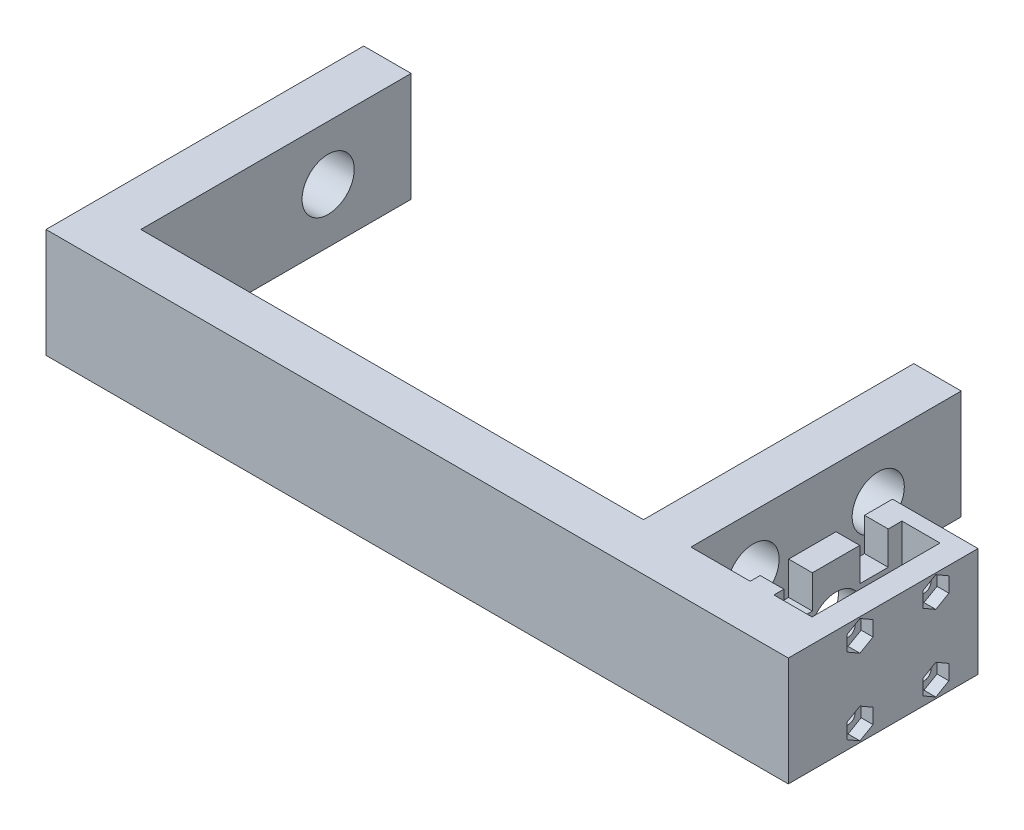
SolidWorks part; units mm, degrees
ref_plane "Front Plane" through (0, 0, 0) normal (0, 0, 1) x (1, 0, 0)
ref_plane "Top Plane" through (0, 0, 0) normal (0, 1, 0) x (1, 0, 0)
ref_plane "Right Plane" through (0, 0, 0) normal (1, 0, 0) x (0, 0, -1)
sketch "Sketch1" plane through (0, 0, 0) normal (0, 1, 0) x (1, 0, 0)
  line L0 (-50, -27.5) -> (-50, 27.5) construction
  line L1 (-40, -17.5) -> (40, -17.5) construction
  line L2 (-40, -17.5) -> (-40, 17.5) construction
  line L3 (-40, 17.5) -> (40, 17.5) construction
  line L4 (40, -17.5) -> (40, 17.5) construction
  line L5 (-40, -17.5) -> (40, 17.5) construction
  line L6 (-40, 17.5) -> (40, -17.5) construction
  line L7 (-50, 27.5) -> (50, 27.5) construction
  line L8 (50, -27.5) -> (50, 27.5) construction
  line L9 (-50, -27.5) -> (50, -27.5) construction
  line L10 (50, 0) -> (53, 0) construction
  line L11 (-50, 0) -> (-53, 0) construction
  line L12 (53, 0) -> (53, -27.5)
  line L13 (53, -27.5) -> (53, -39.5)
  line L14 (-53, 0) -> (-53, -27.5)
  line L15 (-53, -27.5) -> (-53, -39.5)
  line L16 (-53, -39.5) -> (53, -39.5)
  line L17 (53, 0) -> (53, 17.5)
  line L18 (-53, 0) -> (-53, 17.5)
  line L19 (-63, 0) -> (-63, 17.5)
  line L20 (-63, 0) -> (-63, -27.5)
  line L21 (-63, -27.5) -> (-63, -49.5)
  line L22 (-63, -49.5) -> (63, -49.5)
  line L23 (63, -27.5) -> (63, -49.5) construction
  line L24 (63, 0) -> (63, -27.5)
  line L25 (63, 0) -> (63, 17.5)
  line L26 (-53, 17.5) -> (-63, 17.5)
  line L27 (53, 17.5) -> (63, 17.5)
  line L28 (88.54, -39.5) -> (88.54, -9.5)
  line L29 (63, -49.5) -> (88.54, -49.5)
  line L31 (63, -39.5) -> (88.54, -39.5)
  line L32 (88.54, -49.5) -> (88.54, -39.5) construction
  line L33 (88.54, -49.5) -> (93.54, -49.5)
  line L34 (88.54, -49.5) -> (88.54, -9.5) construction
  line L35 (88.54, -9.5) -> (93.54, -9.5)
  line L36 (93.54, -49.5) -> (93.54, -9.5)
  line L37 (63, -39.5) -> (63, 17.5)
  line L39 (75.5, -39.5) -> (80.5, -39.5)
  line L40 (75.5, -39.5) -> (75.5, -9.5)
  line L41 (75.5, -9.5) -> (80.5, -9.5)
  line L42 (80.5, -39.5) -> (80.5, -9.5)
  line L43 (80.5, -9.5) -> (88.54, -9.5)
  line L44 (80.5, -9.5) -> (80.5, -12.5)
  line L45 (80.5, -12.5) -> (88.54, -12.5)
  line L46 (88.54, -9.5) -> (88.54, -12.5)
  point P0 (0, 0)
  point P10 (50, 0)
  point P11 (0, -27.5)
  point P12 (0, 27.5)
  point P13 (-50, 0)
  dimension "D1" = 80
  dimension "D2" = 35
  dimension "D4" = 3
  dimension "D5" = 12
  dimension "D7" = 8.04
  dimension "D8" = 5
  dimension "D9" = 12.5
  dimension "D10" = 5
  dimension "D11" = 30
  dimension "D12" = 3
  dimension "D3" = 10
  dimension "D6" = 10
extrude "Boss-Extrude1" add sketch "Sketch1" along normal mid plane 23 contours L31 L37 L24 L25 L27 L17 L12 L13 L16 L15 L14 L18 L26 L19 L20 L21 L22 L29 L33 L36 L35 L28 | L31 L42 L41 L40 | L42 L45 L28 L43 region at (54.7028, 0, -8.75) region at (78, 0, 24.5) region at (84.52, 0, 11)
sketch "Sketch2" plane through (63, 0, 0) normal (1, 0, 0) x (0, 0, -1)
  line L0 (-23.594, 0) -> (-26.9808, 0) construction
  line L1 (-23.594, 0) -> (-26.394, 0) construction
  line L4 (-39.5, -11.5) -> (17.5, -11.5)
  line L5 (17.5, -11.5) -> (17.5, 11.5)
  line L6 (-39.5, -11.5) -> (17.5, -11.5)
  line L7 (17.5, 11.5) -> (-39.5, 11.5)
  line L9 (17.5, -11.5) -> (17.5, 11.5)
  line L14 (17.5, 11.5) -> (-39.5, 11.5)
  line L15 (-39.5, 11.5) -> (-39.5, -11.5)
  line L16 (-39.5, 11.5) -> (-39.5, -11.5)
  circle A0 centre (0, 0) radius 5.5
  circle A1 centre (0, 0) radius 23.594 construction
  circle A2 centre (-26.394, 0) radius 3.3868 construction
  circle A3 centre (-26.9808, 0) radius 3.3867 construction
  circle A4 centre (-26.394, 0) radius 5.5
  dimension "D2" = 11
  dimension "D3" = 47.188
  dimension "D4" = 3.3868
  dimension "D5" = 2.8
  dimension "D1" = 0
extrude "Cut-Extrude1" cut sketch "Sketch2" against normal up to surface (126 mm away) contours A0 up to face at (-63, 0, 16)
sketch "Sketch3" plane through (63, 0, 0) normal (1, 0, 0) x (0, 0, -1)
  circle A0 centre (-26.394, 0) radius 5.5 construction
  circle A1 centre (-26.394, 0) radius 5.5
extrude "Cut-Extrude2" cut sketch "Sketch3" against normal up to next
sketch "Sketch8" plane through (75.5, 0, 0) normal (-1, 0, 0) x (0, 0, 1)
  circle A0 centre (26.394, 0) radius 5.5 construction
  circle A1 centre (26.394, 0) radius 5.5
extrude "Cut-Extrude5" cut sketch "Sketch8" against normal up to surface (5 mm away) up to face at (80.5, 0, 26)
sketch "Sketch10" plane through (88.54, 0, 0) normal (-1, 0, 0) x (0, 0, 1)
  line L1 (18.394, -8) -> (34.394, -8) construction
  line L2 (18.394, -8) -> (18.394, 8) construction
  line L3 (18.394, 8) -> (34.394, 8) construction
  line L4 (34.394, -8) -> (34.394, 8) construction
  line L5 (18.394, -8) -> (34.394, 8) construction
  line L6 (18.394, 8) -> (34.394, -8) construction
  circle A0 centre (26.394, 0) radius 5.5 construction
  circle A1 centre (26.394, 0) radius 5.5 construction
  circle A2 centre (18.394, 8) radius 1.8
  circle A3 centre (34.394, -8) radius 1.8
  circle A4 centre (18.394, -8) radius 1.8
  circle A5 centre (34.394, 8) radius 1.8
  dimension "D2" = 3.6
  dimension "D1" = 16
extrude "Boss-Extrude4" add sketch "Sketch10" along normal blind 1
sketch "Sketch11" plane through (87.54, 0, 0) normal (-1, 0, 0) x (0, 0, 1)
  circle A0 centre (18.394, 8) radius 1.5
  circle A1 centre (34.394, 8) radius 1.5
  circle A2 centre (34.394, -8) radius 1.5
  circle A3 centre (18.394, -8) radius 1.5
  dimension "D1" = 3
extrude "Cut-Extrude6" cut sketch "Sketch11" against normal up to surface (6 mm away) up to face at (93.54, 0, 29.5)
sketch "Sketch12" plane through (93.54, 0, 0) normal (1, 0, 0) x (0, 0, -1)
  line L1 (-31.644, 9.5877) -> (-34.394, 11.1754)
  line L2 (-34.394, 11.1754) -> (-37.144, 9.5877)
  line L3 (-37.144, 9.5877) -> (-37.144, 6.4123)
  line L4 (-49.5, -11.5) -> (-9.5, -11.5)
  line L5 (-9.5, -11.5) -> (-9.5, 11.5)
  line L6 (-9.5, 11.5) -> (-49.5, 11.5)
  line L7 (-49.5, 11.5) -> (-49.5, -11.5)
  line L8 (-49.5, -11.5) -> (-9.5, -11.5)
  line L9 (-9.5, -11.5) -> (-9.5, 11.5)
  line L10 (-9.5, 11.5) -> (-49.5, 11.5)
  line L11 (-49.5, 11.5) -> (-49.5, -11.5)
  line L12 (-37.144, 6.4123) -> (-34.394, 4.8246)
  line L13 (-34.394, 4.8246) -> (-31.644, 6.4123)
  line L14 (-31.644, 6.4123) -> (-31.644, 9.5877)
  line L15 (-18.394, 11.1754) -> (-21.144, 9.5877)
  line L16 (-21.144, 9.5877) -> (-21.144, 6.4123)
  line L17 (-21.144, 6.4123) -> (-18.394, 4.8246)
  line L18 (-18.394, 4.8246) -> (-15.644, 6.4123)
  line L19 (-15.644, 6.4123) -> (-15.644, 9.5877)
  line L20 (-15.644, 9.5877) -> (-18.394, 11.1754)
  line L21 (-31.644, -6.4123) -> (-34.394, -4.8246)
  line L22 (-34.394, -4.8246) -> (-37.144, -6.4123)
  line L23 (-37.144, -6.4123) -> (-37.144, -9.5877)
  line L24 (-37.144, -9.5877) -> (-34.394, -11.1754)
  line L25 (-34.394, -11.1754) -> (-31.644, -9.5877)
  line L26 (-31.644, -9.5877) -> (-31.644, -6.4123)
  line L27 (-15.644, -6.4123) -> (-18.394, -4.8246)
  line L28 (-18.394, -4.8246) -> (-21.144, -6.4123)
  line L29 (-21.144, -6.4123) -> (-21.144, -9.5877)
  line L30 (-21.144, -9.5877) -> (-18.394, -11.1754)
  line L31 (-18.394, -11.1754) -> (-15.644, -9.5877)
  line L32 (-15.644, -9.5877) -> (-15.644, -6.4123)
  circle A0 centre (-34.394, 8) radius 2.75 construction
  circle A1 centre (-18.394, 8) radius 2.75 construction
  circle A2 centre (-34.394, -8) radius 2.75 construction
  circle A3 centre (-18.394, -8) radius 2.75 construction
  circle M5 centre (-18.394, -8) radius 1.5
  circle M6 centre (-34.394, -8) radius 1.5
  circle M7 centre (-34.394, 8) radius 1.5
  circle M8 centre (-18.394, 8) radius 1.5
  line M11 (-9.5, 11.5) -> (-49.5, 11.5)
  dimension "D2" = 5.5
  dimension "D1" = 0
extrude "Cut-Extrude7" cut sketch "Sketch12" against normal blind 2.5 contours L13 L14 L1 L2 L3 L12 M11 M7 | L19 L20 L10 L15 L16 L17 L18 M8 | L31 L32 L27 L28 L29 L30 L8 M5 | L25 L26 L21 L22 L23 L24 L8 M6 region at (93.54, 8, 31.728) region at (93.54, 10.3088, 17.061) region at (93.54, -8, 31.728) region at (93.54, -8, 15.728)
sketch "Sketch13" plane through (80.5, 0, 0) normal (1, 0, 0) x (0, 0, -1)
  line L0 (-49.5, 11.5) -> (-9.5, 11.5) construction
  line L1 (-37.394, 4.5) -> (-31.394, 4.5)
  line L2 (-37.394, 4.5) -> (-37.394, 11.5)
  line L3 (-37.394, 11.5) -> (-31.394, 11.5)
  line L4 (-31.394, 4.5) -> (-31.394, 11.5)
  line L5 (-37.394, 4.5) -> (-31.394, 11.5) construction
  line L6 (-37.394, 11.5) -> (-31.394, 4.5) construction
  line L7 (-21.394, 4.5) -> (-15.394, 4.5)
  line L8 (-21.394, 4.5) -> (-21.394, 11.5)
  line L9 (-21.394, 11.5) -> (-15.394, 11.5)
  line L10 (-15.394, 4.5) -> (-15.394, 11.5)
  line L11 (-21.394, 4.5) -> (-15.394, 11.5) construction
  line L12 (-21.394, 11.5) -> (-15.394, 4.5) construction
  line L13 (-21.394, -11.5) -> (-15.394, -11.5)
  line L14 (-21.394, -11.5) -> (-21.394, -4.5)
  line L15 (-21.394, -4.5) -> (-15.394, -4.5)
  line L16 (-15.394, -11.5) -> (-15.394, -4.5)
  line L17 (-21.394, -11.5) -> (-15.394, -4.5) construction
  line L18 (-21.394, -4.5) -> (-15.394, -11.5) construction
  line L19 (-37.394, -11.5) -> (-31.394, -11.5)
  line L20 (-37.394, -11.5) -> (-37.394, -4.5)
  line L21 (-37.394, -4.5) -> (-31.394, -4.5)
  line L22 (-31.394, -11.5) -> (-31.394, -4.5)
  line L23 (-37.394, -11.5) -> (-31.394, -4.5) construction
  line L24 (-37.394, -4.5) -> (-31.394, -11.5) construction
  line L25 (-49.5, -11.5) -> (-9.5, -11.5) construction
  circle A0 centre (-34.394, -8) radius 1.5 construction
  circle A1 centre (-18.394, -8) radius 1.5 construction
  circle A2 centre (-18.394, 8) radius 1.5 construction
  circle A3 centre (-34.394, 8) radius 1.5 construction
  circle A4 centre (-34.394, -8) radius 1.5 construction
  circle A5 centre (-18.394, -8) radius 1.5 construction
  circle A6 centre (-18.394, 8) radius 1.5 construction
  circle A7 centre (-34.394, 8) radius 1.5 construction
  point P22 (0, 0)
  point P23 (-18.394, 8)
  point P28 (-18.394, -8)
  point P33 (-34.394, -8)
  dimension "D1" = 6
extrude "Cut-Extrude9" cut sketch "Sketch13" against normal up to surface (5 mm away) up to face at (75.5, 0, 31.894)
equation "\"a\"= 1"
equation "\"b\"= 1"
equation "\"c\"= 1"
equation "\"d\"= 1"
equation "\"e\"= 1"
equation "\"x\"= 1"
equation "\"y\"= 1"
equation "\"z\"= 1"
